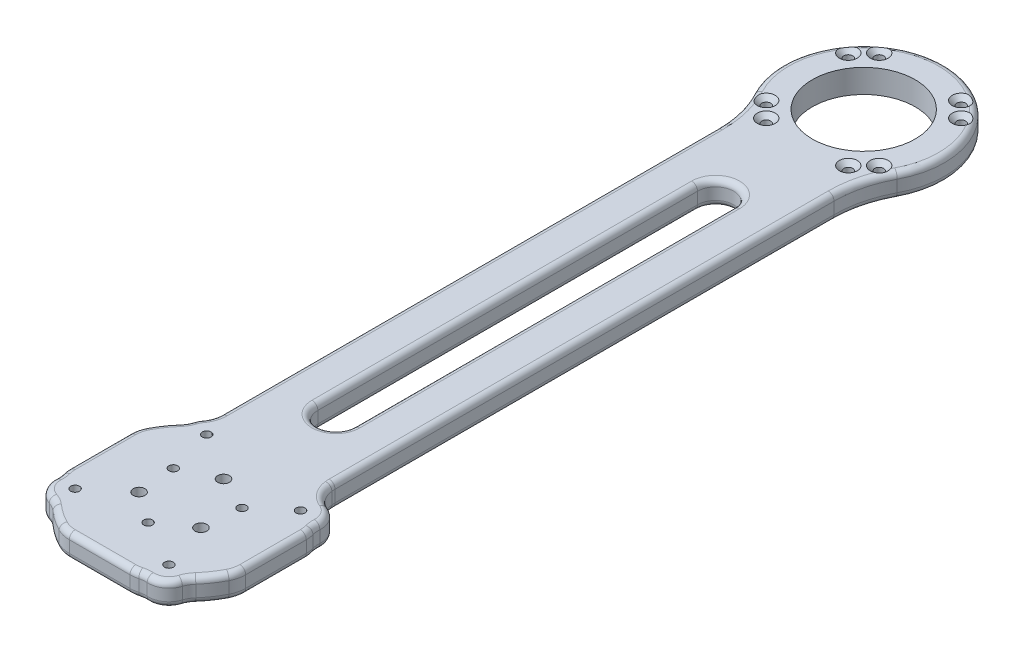
SolidWorks part; units mm, degrees
material "Thornel Mat VMA"
ref_plane "前视基准面" through (0, 0, 0) normal (0, 0, 1) x (1, 0, 0)
ref_plane "上视基准面" through (0, 0, 0) normal (0, 1, 0) x (1, 0, 0)
ref_plane "右视基准面" through (0, 0, 0) normal (1, 0, 0) x (0, 0, -1)
sketch "草图1" plane through (0, 0, 0) normal (0, 1, 0) x (1, 0, 0)
  line L0 (0, -31.6456) -> (0, -164.4547) construction
  line L2 (-30, 145) -> (-30, -145) construction
  line L3 (-30, -145) -> (30, -145) construction
  line L4 (30, 145) -> (30, -145) construction
  line L5 (-30, 145) -> (30, -145) construction
  line L6 (-30, -145) -> (30, 145) construction
  line L7 (-30, -85) -> (30, -85) construction
  line L8 (-30, -85) -> (-30, -145) construction
  line L9 (-30, -145) -> (30, -145) construction
  line L10 (30, -85) -> (30, -145) construction
  line L11 (-30, -85) -> (30, -145) construction
  line L12 (-30, -145) -> (30, -85) construction
  line L13 (-20, -84.896) -> (-20, 84.896)
  line L14 (-30, -104.6922) -> (-30, -125.3078)
  line L15 (-10.3078, -145) -> (10.3078, -145)
  line L16 (30, -104.6922) -> (30, -125.3078)
  line L17 (20, -84.896) -> (20, 84.896)
  line L18 (0, 0) -> (75.3378, 0) construction
  line L19 (0, -115) -> (-15.9693, -92.6118) construction
  line L20 (15.9693, -92.6118) -> (0, -115) construction
  line L21 (-30, 145) -> (30, 145) construction
  line L22 (0, 115) -> (39.9726, 115) construction
  line L23 (-19.2142, 128.9599) -> (0, 115) construction
  line L24 (-13.9599, 134.2142) -> (0, 115) construction
  circle A0 centre (0, -115) radius 32.5 construction
  arc A1 (-22.9412, -91.9793) -> (-28.8889, -100.111) centre (0, -115) ccw
  arc A2 (-28.8889, -129.889) -> (-14.889, -143.8889) centre (0, -115) ccw
  arc A3 (14.889, -143.8889) -> (28.8889, -129.889) centre (0, -115) ccw
  arc A4 (22.9412, -91.9793) -> (28.8889, -100.111) centre (0, -115) cw
  circle A5 centre (0, -115) radius 27.5 construction
  circle A6 centre (-15.9693, -92.6118) radius 1.5
  circle A8 centre (15.9693, -92.6118) radius 1.5
  circle A9 centre (-22.3882, -130.9693) radius 1.5
  circle A10 centre (-22.3882, -99.0307) radius 1.5
  circle A11 centre (-15.9693, -137.3882) radius 1.5
  circle A12 centre (15.9693, -137.3882) radius 1.5
  circle A13 centre (22.3882, -130.9693) radius 1.5
  circle A14 centre (22.3882, -99.0307) radius 1.5
  arc A15 (20, -84.896) -> (22.9412, -91.9793) centre (30, -84.896) ccw
  arc A16 (30, -104.6922) -> (28.8889, -100.111) centre (20, -104.6922) ccw
  arc A17 (28.8889, -129.889) -> (30, -125.3078) centre (20, -125.3078) ccw
  arc A18 (10.3078, -145) -> (14.889, -143.8889) centre (10.3078, -135) ccw
  arc A19 (-14.889, -143.8889) -> (-10.3078, -145) centre (-10.3078, -135) ccw
  arc A20 (-30, -125.3078) -> (-28.8889, -129.889) centre (-20, -125.3078) ccw
  arc A21 (-28.8889, -100.111) -> (-30, -104.6922) centre (-20, -104.6922) ccw
  arc A22 (-20, -84.896) -> (-22.9412, -91.9793) centre (-30, -84.896) cw
  circle A23 centre (0, -115) radius 13.5 construction
  circle A24 centre (0, -115) radius 12.15 construction
  circle A25 centre (0, -102.85) radius 2
  circle A27 centre (10.5222, -121.075) radius 2
  circle A28 centre (-10.5222, -121.075) radius 2
  circle A29 centre (0, -128.5) radius 1.5
  circle A30 centre (-11.6913, -108.25) radius 1.5
  circle A31 centre (11.6913, -108.25) radius 1.5
  circle A34 centre (0, 115) radius 23.75 construction
  circle A62 centre (0, 115) radius 17.5
  circle A63 centre (-19.2142, 128.9599) radius 1.5
  circle A64 centre (-13.9599, 134.2142) radius 1.5
  circle A65 centre (13.9599, 134.2142) radius 1.5
  circle A66 centre (19.2142, 128.9599) radius 1.5
  circle A67 centre (-19.2142, 101.0401) radius 1.5
  circle A68 centre (-13.9599, 95.7858) radius 1.5
  circle A69 centre (13.9599, 95.7858) radius 1.5
  circle A70 centre (19.2142, 101.0401) radius 1.5
  circle A71 centre (0, 115) radius 27.5 construction
  arc A72 (-24.2857, 102.0983) -> (24.2857, 102.0983) centre (0, 115) cw
  arc A73 (-24.2857, 102.0983) -> (-20, 84.896) centre (-56.6667, 84.896) cw
  arc A74 (24.2857, 102.0983) -> (20, 84.896) centre (56.6667, 84.896) ccw
  point P0 (0, 0)
  point P6 (0, -115)
  point P48 (22.981, -92.019)
  point P51 (30, -102.5)
  point P54 (30, -127.5)
  point P57 (12.5, -145)
  point P60 (-12.5, -145)
  point P63 (-30, -127.5)
  point P66 (-30, -102.5)
  point P69 (-22.981, -92.019)
  point P80 (0, -115)
  point P83 (20, 0)
  point P88 (0, -115)
  point P89 (-20, 0)
  dimension "D2" = 65
  dimension "D3" = 3
  dimension "D6" = 10
  dimension "D7" = 27
  dimension "D8" = 24.3
  dimension "D10" = 4
  dimension "D12" = 3
  dimension "D13" = 35
  dimension "D15" = 55
  dimension "D18" = 47.5
  dimension "D19" = 3
  dimension "D22" = 55
  dimension "D1" = 60
  dimension "D4" = 35.5
  dimension "D5" = 35.5
  dimension "D14" = 230
  dimension "D16" = 40
  dimension "D17" = 20
  dimension "D20" = 36
  dimension "D21" = 36
  dimension "D9" = 3
  dimension "D11" = 3
extrude "凸台-拉伸1" add sketch "草图1" along normal blind 8
sketch "草图2" plane through (0, 0, 0) normal (0, -1, 0) x (1, 0, 0)
  line L0 (0, 64.6005) -> (0, -64.6005) construction
  line L1 (6.1519, 64.6005) -> (6.1519, -64.6005)
  line L2 (-6.1519, 64.6005) -> (-6.1519, -64.6005)
  arc A0 (6.1519, 64.6005) -> (-6.1519, 64.6005) centre (0, 64.6005) ccw
  arc A1 (-6.1519, -64.6005) -> (6.1519, -64.6005) centre (0, -64.6005) ccw
  point P2 (0, 0)
extrude "切除-拉伸1" cut sketch "草图2" against normal blind 21.5 and the other way blind 18
chamfer "倒角1" distance 1.55 angle 45 8 edges at (13.9599, 8, -135.7142) (19.2142, 8, -130.4599) (19.2142, 8, -99.5401) (13.9599, 8, -94.2858) (-13.9599, 8, -97.2858) (-19.2142, 8, -102.5401) (-19.2142, 8, -127.4599) (-13.9599, 8, -132.7142)
sketch "草图3" plane through (0, 0, 0) normal (0, -1, 0) x (1, 0, 0)
  line L0 (16.9277, 137.499) -> (16.3266, 136.5131) construction
  circle A0 centre (22.3882, 99.0307) radius 7
  circle A1 centre (15.9693, 137.3882) radius 7
  circle A2 centre (-22.3882, 130.9693) radius 7
  circle A3 centre (-15.9693, 92.6118) radius 7
  circle A4 centre (22.3882, 99.0307) radius 3.8084
  circle A5 centre (-15.9693, 92.6118) radius 3.96
  circle A6 centre (-22.3882, 130.9693) radius 3.96
  circle A7 centre (16.6272, 137.0061) radius 4.1447
  circle A8 centre (15.9693, 92.6118) radius 1.9124
  circle A9 centre (-22.3882, 99.0307) radius 1.8697
  circle A10 centre (-15.9693, 137.3882) radius 1.5773
  circle A11 centre (22.3882, 130.9693) radius 1.8358
  dimension "D1" = 14
extrude "凸台-拉伸2" add sketch "草图3" against normal up to surface (8 mm away) up to face at (13.9599, 8, -137.2642)
fillet "圆角1" radius 8 8 edges at (-22.9406, 4, 91.9788) (14.2741, 4, 144.1798) (22.9406, 4, 138.0212) (-29.1798, 4, 129.2741) (-23.0212, 4, 137.9406) (-20.2378, 4, 87.0638) (29.1798, 4, 100.7259) (23.0212, 4, 92.0594)
fillet "圆角2" radius 2 68 edges at (0, 0, -70.7524) (6.1519, 0, 0) (0, 0, 70.7524) (0, 8, -70.7524) (6.1519, 8, 0) (0, 8, 70.7524) (20.0165, 8, 85.4702) (21.6477, 8, 89.9709) (28.308, 8, 95.2949) (29.4035, 8, 100.7635) (29.9108, 8, 103.3597) (30, 8, 115) (29.7183, 8, 127.6648) (26.8015, 8, 133.3828) (23.3159, 8, 137.9545) (19.9351, 8, 143.1564) (14.2365, 8, 144.4035) (11.6403, 8, 144.9108) (0, 8, 145) (-12.6648, 8, 144.7183) (-18.3828, 8, 141.8015) (-22.9545, 8, 138.3159) (-28.1564, 8, 134.9351) (-29.4035, 8, 129.2365) (-29.9108, 8, 126.6403) (-30, 8, 115) (-29.7183, 8, 102.3352) (-26.8015, 8, 96.6172) (-23.3159, 8, 92.0455) (-22.2011, 8, 89.4236) (-20.4062, 8, 86.1697) (-20, 8, -0.6216) (-21.0876, 8, -93.7601) (0, 8, -142.5) (21.0876, 8, -93.7601) (20.0165, 0, 85.4702) (20, 0, 0) (21.0876, 0, -93.7601) (0, 0, -142.5) (-21.0876, 0, -93.7601) (-20, 0, -0.6216) (-20.4062, 0, 86.1697) (-22.2011, 0, 89.4236) (-23.3159, 0, 92.0455) (-26.8015, 0, 96.6172) (-29.7183, 0, 102.3352) (-30, 0, 115) (-29.9108, 0, 126.6403) (-29.4035, 0, 129.2365) (-28.1564, 0, 134.9351) (-22.9545, 0, 138.3159) (-18.3828, 0, 141.8015) (-12.6648, 0, 144.7183) (0, 0, 145) (11.6403, 0, 144.9108) (14.2365, 0, 144.4035) (19.9351, 0, 143.1564) (23.3159, 0, 137.9545) (26.8015, 0, 133.3828) (29.7183, 0, 127.6648) (30, 0, 115) (29.9108, 0, 103.3597) (29.4035, 0, 100.7635) (28.308, 0, 95.2949) (-6.1519, 0, 0) (-6.1519, 8, 0) (20, 8, 0) (21.6477, 0, 89.9709)
